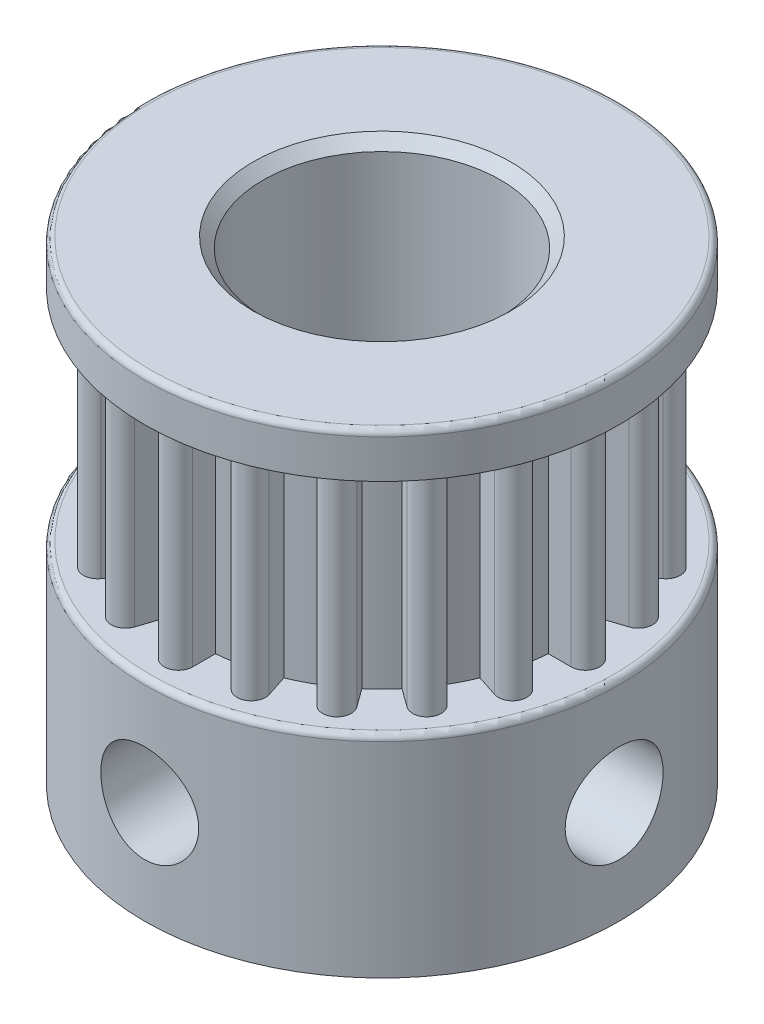
SolidWorks part; units mm, degrees
ref_plane "Front Plane" through (0, 0, 0) normal (0, 0, 1) x (1, 0, 0)
ref_plane "Top Plane" through (0, 0, 0) normal (0, 1, 0) x (1, 0, 0)
ref_plane "Right Plane" through (0, 0, 0) normal (1, 0, 0) x (0, 0, -1)
sketch "Sketch1" plane through (0, 0, 0) normal (0, 1, 0) x (1, 0, 0)
  circle A0 centre (0, 0) radius 8
  circle A1 centre (0, 0) radius 4
  circle A2 centre (0, 0) radius 6.11
  dimension "D1" = 16
  dimension "D2" = 8
  dimension "D3" = 12.22
extrude "Boss-Extrude1" add sketch "Sketch1" against normal blind 7.1 contours A0 A2 | A2 A1 region at (-7.7737, 0, 0) region at (-5.9372, 0, 0)
extrude "Boss-Extrude2" add sketch "Sketch1<3>" along normal blind 7.4 contours A2 A1 region at (-5.9372, 0, 0)
sketch "Sketch1<3>" plane through (0, 0, 0) normal (0, 1, 0) x (1, 0, 0) same geometry as "Sketch1"
sketch "Sketch2" plane through (0, 0, 0) normal (0, 1, 0) x (1, 0, 0)
  line L0 (0, -6.11) -> (0, -6.86) construction
  line L1 (0.4799, -6.86) -> (-0.4799, -6.86) construction
  line L2 (0.4799, -6.86) -> (0.4799, -6.0911)
  line L3 (-0.4799, -6.86) -> (-0.4799, -6.0911)
  line L4 (-1.6635, -6.6725) -> (-1.4259, -5.9413)
  line L5 (-2.5762, -6.376) -> (-2.3387, -5.6447)
  line L6 (-3.644, -5.8319) -> (-3.192, -5.2099)
  line L7 (-4.4204, -5.2678) -> (-3.9685, -4.6458)
  line L8 (-5.2678, -4.4204) -> (-4.6458, -3.9685)
  line L9 (-5.8319, -3.644) -> (-5.2099, -3.192)
  line L10 (-6.376, -2.5762) -> (-5.6447, -2.3387)
  line L11 (-6.6725, -1.6635) -> (-5.9413, -1.4259)
  line L12 (-6.86, -0.4799) -> (-6.0911, -0.4799)
  line L13 (-6.86, 0.4799) -> (-6.0911, 0.4799)
  line L14 (-6.6725, 1.6635) -> (-5.9413, 1.4259)
  line L15 (-6.376, 2.5762) -> (-5.6447, 2.3387)
  line L16 (-5.8319, 3.644) -> (-5.2099, 3.192)
  line L17 (-5.2678, 4.4204) -> (-4.6458, 3.9685)
  line L18 (-4.4204, 5.2678) -> (-3.9685, 4.6458)
  line L19 (-3.644, 5.8319) -> (-3.192, 5.2099)
  line L20 (-2.5762, 6.376) -> (-2.3387, 5.6447)
  line L21 (-1.6635, 6.6725) -> (-1.4259, 5.9413)
  line L22 (-0.4799, 6.86) -> (-0.4799, 6.0911)
  line L23 (0.4799, 6.86) -> (0.4799, 6.0911)
  line L24 (1.6635, 6.6725) -> (1.4259, 5.9413)
  line L25 (2.5762, 6.376) -> (2.3387, 5.6447)
  line L26 (3.644, 5.8319) -> (3.192, 5.2099)
  line L27 (4.4204, 5.2678) -> (3.9685, 4.6458)
  line L28 (5.2678, 4.4204) -> (4.6458, 3.9685)
  line L29 (5.8319, 3.644) -> (5.2099, 3.192)
  line L30 (6.376, 2.5762) -> (5.6447, 2.3387)
  line L31 (6.6725, 1.6635) -> (5.9413, 1.4259)
  line L32 (6.86, 0.4799) -> (6.0911, 0.4799)
  line L33 (6.86, -0.4799) -> (6.0911, -0.4799)
  line L34 (6.6725, -1.6635) -> (5.9413, -1.4259)
  line L35 (6.376, -2.5762) -> (5.6447, -2.3387)
  line L36 (5.8319, -3.644) -> (5.2099, -3.192)
  line L37 (5.2678, -4.4204) -> (4.6458, -3.9685)
  line L38 (4.4204, -5.2678) -> (3.9685, -4.6458)
  line L39 (3.644, -5.8319) -> (3.192, -5.2099)
  line L40 (2.5762, -6.376) -> (2.3387, -5.6447)
  line L41 (1.6635, -6.6725) -> (1.4259, -5.9413)
  circle A0 centre (0, 0) radius 6.11 construction
  circle A1 centre (0, 0) radius 6.11 construction
  arc A2 (-0.4799, -6.86) -> (0.4799, -6.86) centre (0, -6.86) ccw
  arc A3 (-0.4799, -6.0911) -> (0.4799, -6.0911) centre (0, 0) ccw
  arc A4 (-2.5762, -6.376) -> (-1.6635, -6.6725) centre (-2.1199, -6.5242) ccw
  arc A5 (-2.3387, -5.6447) -> (-1.4259, -5.9413) centre (0, 0) ccw
  arc A6 (-4.4204, -5.2678) -> (-3.644, -5.8319) centre (-4.0322, -5.5499) ccw
  arc A7 (-3.9685, -4.6458) -> (-3.192, -5.2099) centre (0, 0) ccw
  arc A8 (-5.8319, -3.644) -> (-5.2678, -4.4204) centre (-5.5499, -4.0322) ccw
  arc A9 (-5.2099, -3.192) -> (-4.6458, -3.9685) centre (0, 0) ccw
  arc A10 (-6.6725, -1.6635) -> (-6.376, -2.5762) centre (-6.5242, -2.1199) ccw
  arc A11 (-5.9413, -1.4259) -> (-5.6447, -2.3387) centre (0, 0) ccw
  arc A12 (-6.86, 0.4799) -> (-6.86, -0.4799) centre (-6.86, 0) ccw
  arc A13 (-6.0911, 0.4799) -> (-6.0911, -0.4799) centre (0, 0) ccw
  arc A14 (-6.376, 2.5762) -> (-6.6725, 1.6635) centre (-6.5242, 2.1199) ccw
  arc A15 (-5.6447, 2.3387) -> (-5.9413, 1.4259) centre (0, 0) ccw
  arc A16 (-5.2678, 4.4204) -> (-5.8319, 3.644) centre (-5.5499, 4.0322) ccw
  arc A17 (-4.6458, 3.9685) -> (-5.2099, 3.192) centre (0, 0) ccw
  arc A18 (-3.644, 5.8319) -> (-4.4204, 5.2678) centre (-4.0322, 5.5499) ccw
  arc A19 (-3.192, 5.2099) -> (-3.9685, 4.6458) centre (0, 0) ccw
  arc A20 (-1.6635, 6.6725) -> (-2.5762, 6.376) centre (-2.1199, 6.5242) ccw
  arc A21 (-1.4259, 5.9413) -> (-2.3387, 5.6447) centre (0, 0) ccw
  arc A22 (0.4799, 6.86) -> (-0.4799, 6.86) centre (0, 6.86) ccw
  arc A23 (0.4799, 6.0911) -> (-0.4799, 6.0911) centre (0, 0) ccw
  arc A24 (2.5762, 6.376) -> (1.6635, 6.6725) centre (2.1199, 6.5242) ccw
  arc A25 (2.3387, 5.6447) -> (1.4259, 5.9413) centre (0, 0) ccw
  arc A26 (4.4204, 5.2678) -> (3.644, 5.8319) centre (4.0322, 5.5499) ccw
  arc A27 (3.9685, 4.6458) -> (3.192, 5.2099) centre (0, 0) ccw
  arc A28 (5.8319, 3.644) -> (5.2678, 4.4204) centre (5.5499, 4.0322) ccw
  arc A29 (5.2099, 3.192) -> (4.6458, 3.9685) centre (0, 0) ccw
  arc A30 (6.6725, 1.6635) -> (6.376, 2.5762) centre (6.5242, 2.1199) ccw
  arc A31 (5.9413, 1.4259) -> (5.6447, 2.3387) centre (0, 0) ccw
  arc A32 (6.86, -0.4799) -> (6.86, 0.4799) centre (6.86, 0) ccw
  arc A33 (6.0911, -0.4799) -> (6.0911, 0.4799) centre (0, 0) ccw
  arc A34 (6.376, -2.5762) -> (6.6725, -1.6635) centre (6.5242, -2.1199) ccw
  arc A35 (5.6447, -2.3387) -> (5.9413, -1.4259) centre (0, 0) ccw
  arc A36 (5.2678, -4.4204) -> (5.8319, -3.644) centre (5.5499, -4.0322) ccw
  arc A37 (4.6458, -3.9685) -> (5.2099, -3.192) centre (0, 0) ccw
  arc A38 (3.644, -5.8319) -> (4.4204, -5.2678) centre (4.0322, -5.5499) ccw
  arc A39 (3.192, -5.2099) -> (3.9685, -4.6458) centre (0, 0) ccw
  arc A40 (1.6635, -6.6725) -> (2.5762, -6.376) centre (2.1199, -6.5242) ccw
  arc A41 (1.4259, -5.9413) -> (2.3387, -5.6447) centre (0, 0) ccw
  point P11 (0, -6.86)
  point P131 (0, 0)
  dimension "D1" = 0.75
  dimension "D2" = 0.9598
  dimension "D3" = 20
extrude "Boss-Extrude3" add sketch "Sketch2" along normal up to surface (7.4 mm away) up to face at (0, 7.4, 4)
sketch "Sketch3" plane through (0, 7.4, 0) normal (0, 1, 0) x (1, 0, 0)
  circle A0 centre (0, 0) radius 8
  circle A1 centre (0, 0) radius 8 construction
  circle A2 centre (0, 0) radius 4
  dimension "D1" = 8
extrude "Boss-Extrude4" add sketch "Sketch3" along normal blind 1.5
fillet "Fillet2" radius 0.2 2 edges at (0, 0, 8) (0, 8.9, 8)
chamfer "Chamfer2" distance 0.35 angle 45 1 edges at (0, 8.9, 4)
sketch "Sketch5" plane through (0, 0, 0) normal (1, 0, 0) x (0, 0, -1)
  line L0 (0, -0.2) -> (0, -7.1) construction
  line L1 (8, -7.1) -> (-8, -7.1) construction
  line L2 (8, -7.1) -> (8, -0.2) construction
  line L3 (8, -0.2) -> (-8, -0.2) construction
  line L4 (-8, -7.1) -> (-8, -0.2) construction
  circle A0 centre (0, -3.65) radius 1.65
  dimension "D1" = 3.3
extrude "Cut-Extrude2" cut sketch "Sketch5" against normal through all both and the other way through all
pattern_circular "CirPattern1" count 2 every 90 about axis through (0, -7.1, 0) along (0, 1, 0) of "Cut-Extrude2"
